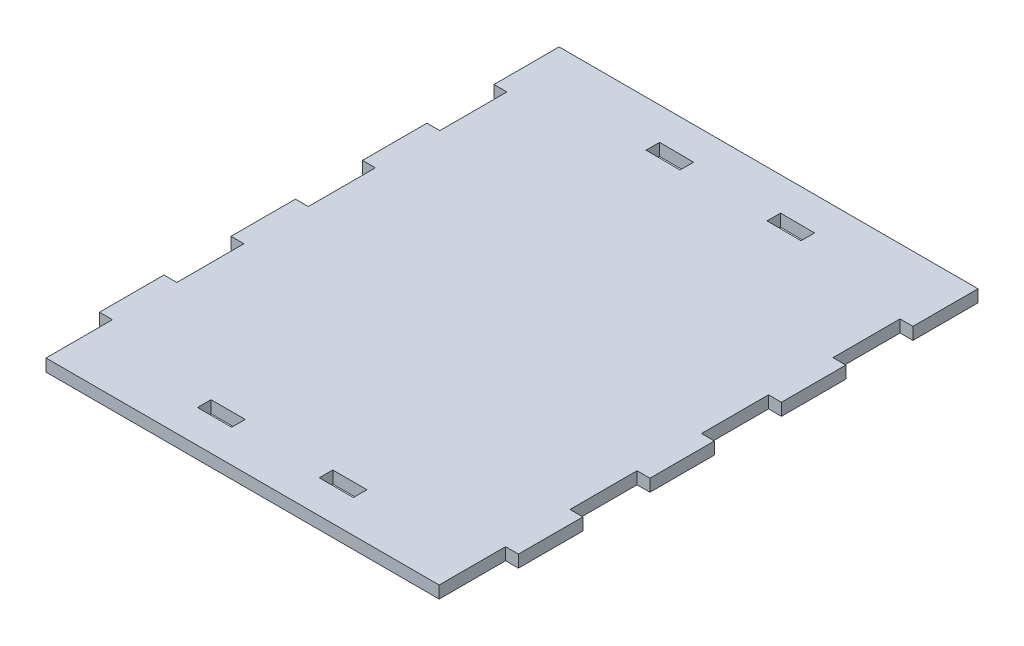
SolidWorks part; units mm, degrees
ref_plane "Front Plane" through (0, 0, 0) normal (0, 0, 1) x (1, 0, 0)
ref_plane "Top Plane" through (0, 0, 0) normal (0, 1, 0) x (1, 0, 0)
ref_plane "Right Plane" through (0, 0, 0) normal (1, 0, 0) x (0, 0, -1)
sketch "Sketch1" plane through (0, 0, 0) normal (0, 1, 0) x (1, 0, 0)
  line L0 (0, 0) -> (76.2, 0)
  line L1 (76.2, 12.7) -> (78.6892, 12.7)
  line L2 (78.6892, 12.7) -> (78.6892, 25.4)
  line L3 (78.6892, 25.4) -> (76.2, 25.4)
  line L4 (76.2, 25.4) -> (76.2, 38.1)
  line L5 (76.2, 38.1) -> (78.6892, 38.1)
  line L6 (78.6892, 38.1) -> (78.6892, 50.8)
  line L7 (78.6892, 50.8) -> (76.2, 50.8)
  line L8 (76.2, 50.8) -> (76.2, 63.5)
  line L9 (76.2, 63.5) -> (78.6892, 63.5)
  line L10 (78.6892, 63.5) -> (78.6892, 76.2)
  line L11 (78.6892, 76.2) -> (76.2, 76.2)
  line L12 (76.2, 76.2) -> (76.2, 88.9)
  line L13 (76.2, 88.9) -> (78.6892, 88.9)
  line L14 (78.6892, 88.9) -> (78.6892, 101.6)
  line L15 (78.6892, 101.6) -> (-2.4892, 101.6)
  line L16 (-2.4892, 101.6) -> (-2.4892, 88.9)
  line L17 (-2.4892, 88.9) -> (0, 88.9)
  line L18 (0, 88.9) -> (0, 76.2)
  line L19 (0, 76.2) -> (-2.4892, 76.2)
  line L20 (-2.4892, 76.2) -> (-2.4892, 63.5)
  line L21 (-2.4892, 63.5) -> (0, 63.5)
  line L22 (0, 63.5) -> (0, 50.8)
  line L23 (0, 50.8) -> (-2.4892, 50.8)
  line L24 (-2.4892, 50.8) -> (-2.4892, 38.1)
  line L25 (-2.4892, 38.1) -> (0, 38.1)
  line L26 (0, 38.1) -> (0, 25.4)
  line L27 (0, 25.4) -> (-2.4892, 25.4)
  line L28 (-2.4892, 25.4) -> (-2.4892, 12.7)
  line L29 (-2.4892, 12.7) -> (0, 12.7)
  line L30 (0, 12.7) -> (0, 0)
  line L31 (76.2, 12.7) -> (76.2, 0)
  line L32 (38.1, 0) -> (38.1, 101.6) construction
  dimension "D1" = 38.1
  dimension "D2" = 12.7
  dimension "D3" = 2.4892
extrude "Boss-Extrude1" add sketch "Sketch1" along normal blind 2.3622
sketch "Sketch2" plane through (0, 2.3622, 0) normal (0, 1, 0) x (1, 0, 0)
  line L0 (-2.4892, 101.6) -> (-2.4892, 88.9)
  line L1 (-2.4892, 88.9) -> (0, 88.9)
  line L2 (0, 88.9) -> (0, 76.2)
  line L3 (0, 76.2) -> (-2.4892, 76.2)
  line L4 (-2.4892, 76.2) -> (-2.4892, 63.5)
  line L5 (-2.4892, 63.5) -> (0, 63.5)
  line L6 (0, 63.5) -> (0, 50.8)
  line L7 (0, 50.8) -> (-2.4892, 50.8)
  line L8 (-2.4892, 50.8) -> (-2.4892, 38.1)
  line L9 (-2.4892, 38.1) -> (0, 38.1)
  line L10 (0, 38.1) -> (0, 25.4)
  line L11 (0, 25.4) -> (-2.4892, 25.4)
  line L12 (-2.4892, 25.4) -> (-2.4892, 12.7)
  line L15 (-2.4892, 12.7) -> (0, 12.7)
  line L16 (0, 12.7) -> (0, 0)
  line L17 (-2.3622, 101.6) -> (-2.3622, 89.027)
  line L18 (-2.3622, 89.027) -> (0.127, 89.027)
  line L19 (0.127, 89.027) -> (0.127, 76.073)
  line L20 (0.127, 76.073) -> (-2.3622, 76.073)
  line L21 (-2.3622, 76.073) -> (-2.3622, 63.627)
  line L22 (-2.3622, 63.627) -> (0.127, 63.627)
  line L23 (0.127, 63.627) -> (0.127, 50.673)
  line L24 (0.127, 50.673) -> (-2.3622, 50.673)
  line L25 (-2.3622, 50.673) -> (-2.3622, 38.227)
  line L26 (-2.3622, 38.227) -> (0.127, 38.227)
  line L27 (0.127, 38.227) -> (0.127, 25.273)
  line L28 (0.127, 25.273) -> (-2.3622, 25.273)
  line L29 (-2.3622, 25.273) -> (-2.3622, 12.827)
  line L30 (-2.3622, 12.827) -> (0.127, 12.827)
  line L31 (0.127, 12.827) -> (0.127, 0)
  line L32 (0, 0) -> (0.127, 0)
  line L33 (-2.3622, 101.6) -> (-2.4892, 101.6)
  line L34 (38.1, 101.6) -> (38.1, 0) construction
  line L35 (78.6892, 101.6) -> (-2.4892, 101.6) construction
  line L36 (0, 0) -> (76.2, 0) construction
  line L37 (78.5622, 101.6) -> (78.6892, 101.6)
  line L38 (76.2, 0) -> (76.073, 0)
  line L39 (76.073, 12.827) -> (76.073, 0)
  line L40 (78.5622, 12.827) -> (76.073, 12.827)
  line L41 (78.5622, 25.273) -> (78.5622, 12.827)
  line L42 (76.073, 25.273) -> (78.5622, 25.273)
  line L43 (76.073, 38.227) -> (76.073, 25.273)
  line L44 (78.5622, 38.227) -> (76.073, 38.227)
  line L45 (78.5622, 50.673) -> (78.5622, 38.227)
  line L46 (76.073, 50.673) -> (78.5622, 50.673)
  line L47 (76.073, 63.627) -> (76.073, 50.673)
  line L48 (78.5622, 63.627) -> (76.073, 63.627)
  line L49 (78.5622, 76.073) -> (78.5622, 63.627)
  line L50 (76.073, 76.073) -> (78.5622, 76.073)
  line L51 (76.073, 89.027) -> (76.073, 76.073)
  line L52 (78.5622, 89.027) -> (76.073, 89.027)
  line L53 (78.5622, 101.6) -> (78.5622, 89.027)
  line L54 (76.2, 12.7) -> (76.2, 0)
  line L55 (78.6892, 12.7) -> (76.2, 12.7)
  line L56 (78.6892, 25.4) -> (78.6892, 12.7)
  line L57 (76.2, 25.4) -> (78.6892, 25.4)
  line L58 (76.2, 38.1) -> (76.2, 25.4)
  line L59 (78.6892, 38.1) -> (76.2, 38.1)
  line L60 (78.6892, 50.8) -> (78.6892, 38.1)
  line L61 (76.2, 50.8) -> (78.6892, 50.8)
  line L62 (76.2, 63.5) -> (76.2, 50.8)
  line L63 (78.6892, 63.5) -> (76.2, 63.5)
  line L64 (78.6892, 76.2) -> (78.6892, 63.5)
  line L65 (76.2, 76.2) -> (78.6892, 76.2)
  line L66 (76.2, 88.9) -> (76.2, 76.2)
  line L67 (78.6892, 88.9) -> (76.2, 88.9)
  line L68 (78.6892, 101.6) -> (78.6892, 88.9)
  line M1 (76.2, 0) -> (76.2, 12.7)
  line M2 (76.2, 12.7) -> (78.6892, 12.7)
  line M3 (78.6892, 12.7) -> (78.6892, 25.4)
  line M4 (78.6892, 25.4) -> (76.2, 25.4)
  line M5 (76.2, 25.4) -> (76.2, 38.1)
  line M6 (76.2, 38.1) -> (78.6892, 38.1)
  line M7 (78.6892, 38.1) -> (78.6892, 50.8)
  line M8 (78.6892, 50.8) -> (76.2, 50.8)
  line M9 (76.2, 50.8) -> (76.2, 63.5)
  line M10 (76.2, 63.5) -> (78.6892, 63.5)
  line M11 (78.6892, 63.5) -> (78.6892, 76.2)
  line M12 (78.6892, 76.2) -> (76.2, 76.2)
  line M13 (76.2, 76.2) -> (76.2, 88.9)
  line M14 (76.2, 88.9) -> (78.6892, 88.9)
  line M15 (78.6892, 88.9) -> (78.6892, 101.6)
  line M16 (78.6892, 101.6) -> (-2.4892, 101.6)
  line M17 (-2.4892, 101.6) -> (-2.4892, 88.9)
  line M18 (-2.4892, 88.9) -> (0, 88.9)
  line M19 (0, 88.9) -> (0, 76.2)
  line M20 (0, 76.2) -> (-2.4892, 76.2)
  line M21 (-2.4892, 76.2) -> (-2.4892, 63.5)
  line M22 (-2.4892, 63.5) -> (0, 63.5)
  line M23 (0, 63.5) -> (0, 50.8)
  line M24 (0, 50.8) -> (-2.4892, 50.8)
  line M25 (-2.4892, 50.8) -> (-2.4892, 38.1)
  line M26 (-2.4892, 38.1) -> (0, 38.1)
  line M27 (0, 38.1) -> (0, 25.4)
  line M28 (0, 25.4) -> (-2.4892, 25.4)
  line M29 (-2.4892, 25.4) -> (-2.4892, 12.7)
  line M30 (-2.4892, 12.7) -> (0, 12.7)
  line M31 (0, 12.7) -> (0, 0)
  line M32 (0, 0) -> (76.2, 0)
  dimension "D1" = 0.127
extrude "Cut-Extrude1" cut sketch "Sketch2" against normal through all contours L53 L52 L51 L50 L49 L48 L47 L46 L45 L44 L43 L42 L41 L40 L39 M16 M32 M1 M2 M3 M4 M5 M6 M7 M8 M9 M10 M11 M12 M13 M14 M15 | L31 L30 L29 L28 L27 L26 L25 L24 L23 L22 L21 L20 L19 L18 L17 M16 M17 M18 M19 M20 M21 M22 M23 M24 M25 M26 M27 M28 M29 M30 M31 M32 region at (-2.4257, 2.3622, -100.5837) region at (78.6257, 2.3622, -100.5837)
sketch "Sketch3" plane through (0, 0, 0) normal (0, -1, 0) x (1, 0, 0)
  line L0 (0.127, -6.35) -> (76.073, -6.35) construction
  line L1 (0.127, -12.827) -> (0.127, 0) construction
  line L2 (76.073, -12.827) -> (76.073, 0) construction
  line L3 (0.127, 0) -> (76.073, 0) construction
  line L4 (38.1, 0) -> (38.1, -101.6) construction
  line L5 (23.0378, -6.35) -> (29.6418, -6.35)
  line L6 (23.0378, -6.35) -> (23.0378, -8.9662)
  line L7 (23.0378, -8.9662) -> (29.6418, -8.9662)
  line L8 (29.6418, -6.35) -> (29.6418, -8.9662)
  line L9 (78.5622, -101.6) -> (-2.3622, -101.6) construction
  line L10 (-2.3622, -25.273) -> (-2.3622, -12.827) construction
  line L11 (46.5582, -6.35) -> (46.5582, -8.9662)
  line L12 (53.1622, -8.9662) -> (46.5582, -8.9662)
  line L13 (53.1622, -6.35) -> (53.1622, -8.9662)
  line L14 (53.1622, -6.35) -> (46.5582, -6.35)
  line L15 (38.1, -50.8) -> (78.5622, -50.673) construction
  line L16 (23.3007, -92.7275) -> (29.9046, -92.6861)
  line L17 (23.3171, -95.3437) -> (23.3007, -92.7275)
  line L18 (23.3171, -95.3437) -> (29.921, -95.3022)
  line L19 (29.921, -95.3022) -> (29.9046, -92.6861)
  line L20 (46.8371, -95.196) -> (46.8206, -92.5799)
  line L21 (53.4245, -92.5384) -> (46.8206, -92.5799)
  line L22 (53.4409, -95.1546) -> (46.8371, -95.196)
  line L23 (53.4409, -95.1546) -> (53.4245, -92.5384)
  dimension "D1" = 6.35
  dimension "D2" = 6.604
  dimension "D3" = 2.6162
  dimension "D4" = 25.4
extrude "Cut-Extrude2" cut sketch "Sketch3" against normal through all
sketch "Sketch5" plane through (0, 0, 0) normal (0, -1, 0) x (1, 0, 0)
  line L0 (38.1, 0) -> (38.1, -101.6) construction
  line L1 (0.127, 0) -> (76.073, 0) construction
  line L2 (78.5622, -101.6) -> (-2.3622, -101.6) construction
  text T0 "<b>Olin Swarmbots</b>" font "Stencil Std" height in points 24
extrude "Cut-Extrude3" cut sketch "Sketch5" against normal blind 0.127
